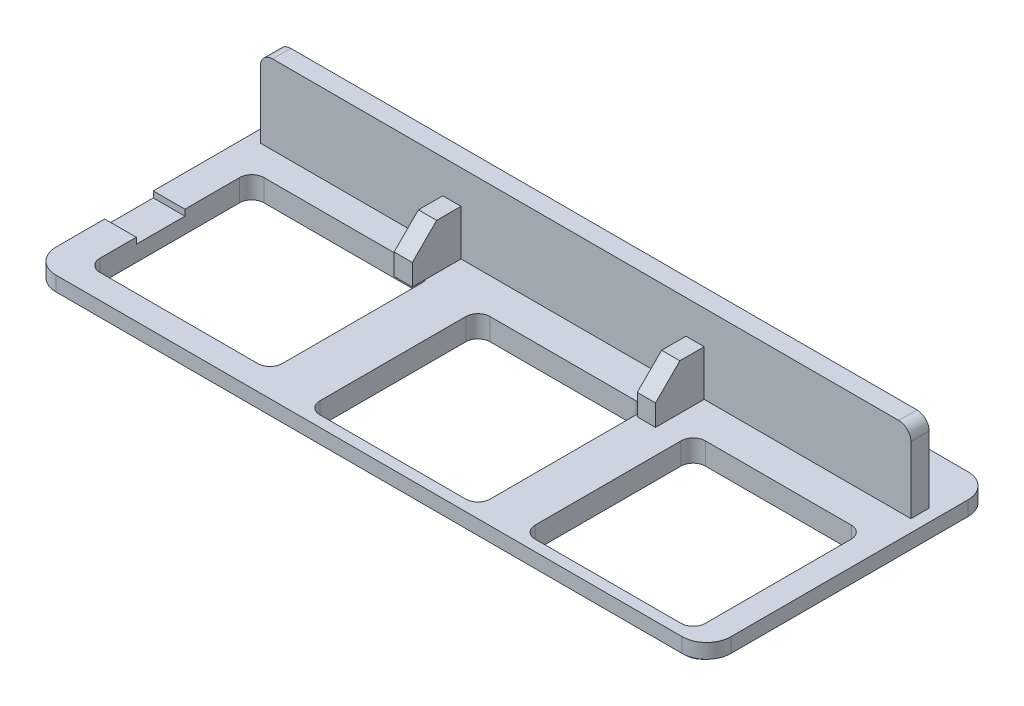
SolidWorks part; units mm, degrees
ref_plane "前视基准面" through (0, 0, 0) normal (0, 0, 1) x (1, 0, 0)
ref_plane "上视基准面" through (0, 0, 0) normal (0, 1, 0) x (1, 0, 0)
ref_plane "右视基准面" through (0, 0, 0) normal (1, 0, 0) x (0, 0, -1)
sketch "草图1" plane through (0, 0, 0) normal (0, 1, 0) x (1, 0, 0)
  line L1 (-27.75, 11.75) -> (27.75, 11.75)
  line L2 (-27.75, 11.75) -> (-27.75, -11.75)
  line L3 (-27.75, -11.75) -> (27.75, -11.75)
  line L4 (27.75, 11.75) -> (27.75, -11.75)
  line L5 (-27.75, 11.75) -> (27.75, -11.75) construction
  line L6 (-27.75, -11.75) -> (27.75, 11.75) construction
  point P0 (0, 0)
  dimension "D1" = 23.5
  dimension "D2" = 55.5
extrude "凸台-拉伸1" add sketch "草图1" along normal blind 1.2
fillet "圆角1" radius 2 4 edges at (-27.75, 0.6, 11.75) (27.75, 0.6, 11.75) (-27.75, 0.6, -11.75) (27.75, 0.6, -11.75)
sketch "草图2" plane through (0, 0, 0) normal (0, -1, 0) x (1, 0, 0)
  line L0 (-27.75, -9.75) -> (-27.75, 9.75) construction
  line L1 (-26.85, 11.15) -> (26.85, 11.15)
  line L2 (-26.85, 11.15) -> (-26.85, -11.15)
  line L3 (-26.85, -11.15) -> (26.85, -11.15)
  line L4 (26.85, 11.15) -> (26.85, -11.15)
  line L5 (27.75, 9.75) -> (27.75, -9.75) construction
  line L6 (-25.75, 11.75) -> (25.75, 11.75) construction
  line L7 (25.75, -11.75) -> (-25.75, -11.75) construction
  dimension "D1" = 0.9
  dimension "D2" = 0.9
  dimension "D3" = 0.6
  dimension "D4" = 0.6
extrude "凸台-拉伸2" add sketch "草图2" along normal blind 0.6
sketch "草图3" plane through (0, -0.6, 0) normal (0, -1, 0) x (1, 0, 0)
  line L1 (-25.15, 9.75) -> (-10.15, 9.75)
  line L2 (-25.15, 9.75) -> (-25.15, -3.75)
  line L3 (-25.15, -3.75) -> (-10.15, -3.75)
  line L4 (-10.15, 9.75) -> (-10.15, -3.75)
  line L5 (-5.95, 10.85) -> (8.05, 10.85)
  line L6 (-5.95, 10.85) -> (-5.95, -3.15)
  line L7 (-5.95, -3.15) -> (8.05, -3.15)
  line L8 (8.05, 10.85) -> (8.05, -3.15)
  line L9 (11.75, 10.85) -> (25.75, 10.85)
  line L10 (11.75, 10.85) -> (11.75, -3.15)
  line L11 (11.75, -3.15) -> (25.75, -3.15)
  line L12 (25.75, 10.85) -> (25.75, -3.15)
  line L15 (-27.75, -9.75) -> (-27.75, 9.75) construction
  line L16 (-25.75, 11.75) -> (25.75, 11.75) construction
  line L17 (27.75, 9.75) -> (27.75, -9.75) construction
  dimension "D1" = 15
  dimension "D2" = 14
  dimension "D3" = 14
  dimension "D4" = 2.6
  dimension "D5" = 2
  dimension "D6" = 21.8
  dimension "D7" = 14
  dimension "D8" = 2
  dimension "D9" = 0.9
  dimension "D10" = 13.5
extrude "切除-拉伸1" cut sketch "草图3" against normal blind 3
fillet "圆角2" radius 1 12 edges at (-25.15, 0.3, 9.75) (-10.15, 0.3, 9.75) (-5.95, 0.3, 10.85) (8.05, 0.3, 10.85) (25.75, 0.3, 10.85) (11.75, 0.3, 10.85) (25.75, 0.3, -3.15) (11.75, 0.3, -3.15) (8.05, 0.3, -3.15) (-5.95, 0.3, -3.15) (-10.15, 0.3, -3.75) (-25.15, 0.3, -3.75)
sketch "草图4" plane through (0, 1.2, 0) normal (0, 1, 0) x (1, 0, 0)
  line L0 (-27.75, 9.75) -> (-27.75, -9.75) construction
  line L1 (-12.25, -5.75) -> (-27.75, -5.75)
  line L2 (-12.25, -5.75) -> (-12.25, -1.7526)
  line L3 (-12.25, -1.7526) -> (-27.75, -1.7526)
  line L4 (-27.75, -5.75) -> (-27.75, -1.7526)
  line L5 (-25.75, -11.75) -> (25.75, -11.75) construction
  dimension "D1" = 6
  dimension "D2" = 3.9974
  dimension "D3" = 15.5
extrude "切除-拉伸2" cut sketch "草图4" against normal blind 0.5
sketch "草图5" plane through (0, 1.2, 0) normal (0, 1, 0) x (1, 0, 0)
  line L1 (26.75, 6.0546) -> (-26.75, 6.0546)
  line L2 (26.75, 6.0546) -> (26.75, 7.5546)
  line L3 (26.75, 7.5546) -> (-26.75, 7.5546)
  line L4 (-26.75, 6.0546) -> (-26.75, 7.5546)
  line L6 (-27.75, 9.75) -> (-27.75, -1.7526) construction
  line L7 (27.75, -9.75) -> (27.75, 9.75) construction
  line L8 (25.75, 11.75) -> (-25.75, 11.75) construction
  dimension "D1" = 1.5
  dimension "D2" = 1
  dimension "D3" = 1
  dimension "D4" = 4.1954
extrude "凸台-拉伸3" add sketch "草图5" along normal blind 6.5
fillet "圆角3" radius 1 2 edges at (-26.75, 7.7, -6.8046) (26.75, 7.7, -6.8046)
sketch "草图6" plane through (0, 1.2, 0) normal (0, 1, 0) x (1, 0, 0)
  line L0 (-26.75, 6.0546) -> (26.75, 6.0546) construction
  line L1 (9.75, 6.0546) -> (8.25, 6.0546)
  line L2 (9.75, 6.0546) -> (9.75, 2.0546)
  line L3 (9.75, 2.0546) -> (8.25, 2.0546)
  line L4 (8.25, 6.0546) -> (8.25, 2.0546)
  line L5 (27.75, -9.75) -> (27.75, 9.75) construction
  line L6 (-10.25, 6.0546) -> (-11.75, 6.0546)
  line L7 (-10.25, 6.0546) -> (-10.25, 2.0546)
  line L8 (-10.25, 2.0546) -> (-11.75, 2.0546)
  line L9 (-11.75, 6.0546) -> (-11.75, 2.0546)
  line L10 (-27.75, -5.75) -> (-27.75, -9.75) construction
  dimension "D1" = 4
  dimension "D2" = 1.5
  dimension "D3" = 18
  dimension "D4" = 16
extrude "凸台-拉伸4" add sketch "草图6" along normal blind 3.75
chamfer "倒角1" distance 2 angle 45 2 edges at (-11, 4.95, -2.0546) (9, 4.95, -2.0546)
fillet "圆角4" radius 1.5 4 edges at (-26.85, -0.3, -11.15) (26.85, -0.3, -11.15) (26.85, -0.3, 11.15) (-26.85, -0.3, 11.15)
